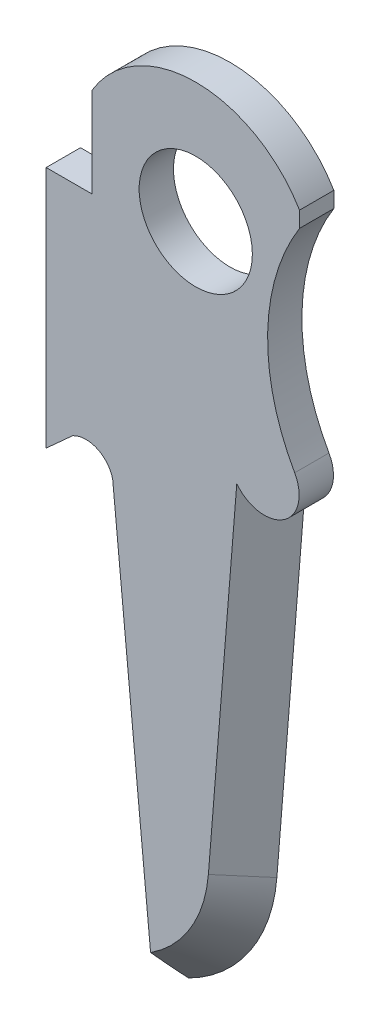
SolidWorks part; units mm, degrees
material "Plain Carbon Steel"
ref_plane "Front Plane" through (0, 0, 0) normal (0, 0, 1) x (1, 0, 0)
ref_plane "Top Plane" through (0, 0, 0) normal (0, 1, 0) x (1, 0, 0)
ref_plane "Right Plane" through (0, 0, 0) normal (1, 0, 0) x (0, 0, -1)
sketch "Sketch1" plane through (0, 0, 0) normal (0, 0, 1) x (1, 0, 0)
  line L0 (15.0593, 33.8835) -> (75.2966, 33.8835) construction
  line L1 (41.3461, 38.2231) -> (41.3461, 29.227)
  line L2 (41.3461, 29.227) -> (42.3274, 30.116)
  line L3 (41.3461, 38.2231) -> (43.0416, 38.2231)
  line L4 (43.0416, 38.2231) -> (43.0416, 41.546)
  line L8 (49.6371, 31.132) -> (48.6166, 18.4608)
  line L12 (50.725, 41.546) -> (50.725, 40.9618)
  line L13 (43.8092, 29.4556) -> (45.3459, 13.606)
  arc A1 (45.3459, 13.606) -> (48.6166, 18.4608) centre (42.6669, 18.94) ccw
  arc A2 (43.8092, 29.4556) -> (42.3274, 30.116) centre (42.8193, 29.227) ccw
  arc A3 (50.725, 41.546) -> (43.0416, 41.546) centre (46.8833, 39.26) ccw
  arc A4 (50.725, 40.9618) -> (50.5448, 33.0351) centre (57.2973, 36.847) ccw
  arc A5 (49.6371, 31.132) -> (50.5448, 33.0351) centre (49.4233, 32.402) ccw
  point P8 (0, 0)
  point P9 (0, 0)
  point P10 (0, 0)
  point P11 (0, 0)
  point P16 (0, 0)
  dimension "D3" = 1.0369
  dimension "D4" = 2.286
  dimension "D5" = 10.414
  dimension "D6" = 2.413
  dimension "D7" = 6.858
  dimension "D1" = 4.4704
  dimension "D13" = 1.016
  dimension "D17" = 5.969
  dimension "D2" = 1.7018
  dimension "D8" = 2.54
  dimension "D10" = 5.5372
  dimension "D11" = 10.033
  dimension "D12" = 4.064
  dimension "D14" = 9.144
  dimension "D15" = 25.654
  dimension "D16" = 9.8044
  dimension "D18" = 20.32
  dimension "D19" = 4.2164
  dimension "D20" = 8.128
extrude "Boss-Extrude1" add sketch "Sketch1" along normal blind 1.27
sketch "Sketch2" plane through (0, 0, 1.27) normal (0, 0, 1) x (1, 0, 0)
  circle A0 centre (46.8833, 39.26) radius 2.0955
  dimension "D1" = 4.191
extrude "Cut-Extrude1" cut sketch "Sketch2" against normal through all
chamfer "Chamfer1" distance 1.27 angle 45 2 edges at (47.6173, 15.6049, 1.27) (49.1268, 24.7964, 1.27)
